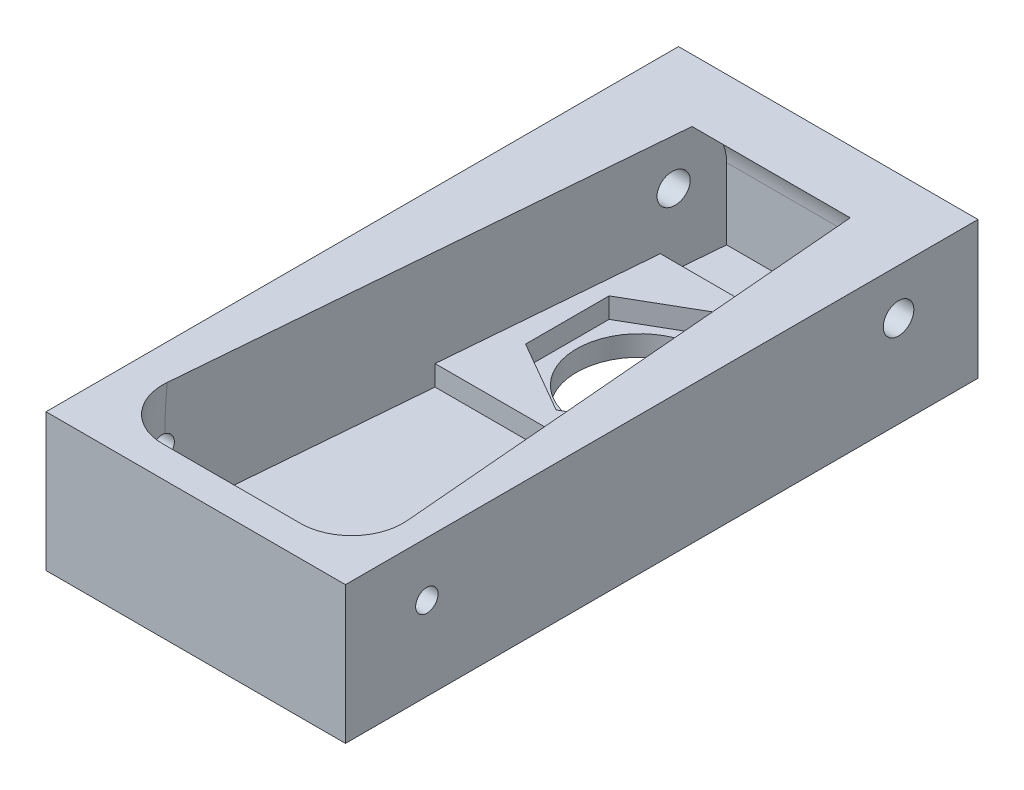
SolidWorks part; units mm, degrees
ref_plane "Front Plane" through (0, 0, 0) normal (0, 0, 1) x (1, 0, 0)
ref_plane "Top Plane" through (0, 0, 0) normal (0, 1, 0) x (1, 0, 0)
ref_plane "Right Plane" through (0, 0, 0) normal (1, 0, 0) x (0, 0, -1)
sketch "Sketch1" plane through (0, 0, 0) normal (0, 1, 0) x (1, 0, 0)
  line L0 (-15.3875, 18.6983) -> (-12.3875, 15.6983) construction
  line L1 (-12.3875, 15.6983) -> (12.0569, 15.6983) construction
  line L2 (-12.3875, 15.6983) -> (-12.3875, -40.3917) construction
  line L3 (-12.3875, -40.3917) -> (12.0569, -40.3917) construction
  line L4 (12.0569, 15.6983) -> (12.0569, -40.3917) construction
  line L5 (-15.3875, 18.6983) -> (14.0125, 18.6983)
  line L6 (-15.3875, 18.6983) -> (-15.3875, -43.3917)
  line L7 (-15.3875, -43.3917) -> (14.0125, -43.3917)
  line L8 (14.0125, 18.6983) -> (14.0125, -43.3917)
  line L9 (12.0569, -40.3917) -> (14.0125, -43.3917) construction
  line L10 (12.0569, 15.6983) -> (14.0125, 18.6983) construction
  line L11 (-12.3875, -40.3917) -> (-15.3875, -43.3917) construction
  line L12 (-12.3875, -40.3917) -> (-12.0875, -40.0917) construction
  line L13 (-12.0875, 15.3983) -> (11.7569, 15.3983) construction
  line L14 (-12.0875, 15.3983) -> (-12.0875, -40.0917) construction
  line L15 (-12.0875, -40.0917) -> (11.7569, -40.0917) construction
  line L16 (11.7569, 15.3983) -> (11.7569, -40.0917) construction
  line L17 (11.7569, -40.0917) -> (12.0569, -40.3917) construction
  line L18 (11.7569, 15.3983) -> (12.0569, 15.6983) construction
  line L19 (-12.3875, 15.6983) -> (-12.0875, 15.3983) construction
  line L20 (-7.6345, 15.6983) -> (-7.6345, 18.6983) construction
  line L21 (-12.3875, -10.0633) -> (-15.3875, -10.0633) construction
  line L22 (-7.6345, 15.6983) -> (-7.6345, 15.3983) construction
  line L23 (-12.3875, -10.0633) -> (-12.0875, -10.0633) construction
  line L24 (-15.3875, 18.6983) -> (14.0125, 18.6983) construction
  line L25 (14.0125, 18.6983) -> (14.0125, -43.3917) construction
  dimension "D1" = 3
  dimension "D2" = 0.3
extrude "Boss-Extrude1" add sketch "Sketch1" against normal blind 11.5
sketch "Sketch3" plane through (0, 0, 0) normal (1, 0, 0) x (0, 0, -1)
  line L3 (15.6983, -4.5) -> (15.6983, -55.7628)
  line L4 (15.6983, 0) -> (15.6983, -4.5) construction
  line L5 (15.6983, 0) -> (10.8983, 0) construction
  line L6 (15.6983, 0) -> (18.6983, 0) construction
  line L8 (-40.0905, 0) -> (-40.3917, 0)
  line L9 (12.5687, 0) -> (10.8983, 0)
  line L11 (10.8983, 0) -> (-40.0905, 0)
  arc A0 (-40.3917, 0) -> (15.6983, -55.7628) centre (10.8983, -4.5) ccw
  circle A1 centre (10.8983, -4.5) radius 1.5 construction
  circle A2 centre (10.8983, -4.5) radius 4.8 construction
  circle A3 centre (10.8983, -4.5) radius 4.5 construction
  circle A5 centre (10.8983, -4.5) radius 51.1871 construction
  arc A6 (15.6983, -4.5) -> (12.5687, 0) centre (10.8983, -4.5) ccw
  point P8 (0, 0)
  dimension "D1" = 3
  dimension "D2" = 3
  dimension "D3" = 0.3
  dimension "D4" = 3
  dimension "D5" = 0.3
extrude "Cut-Extrude2" cut sketch "Sketch3" against normal up to vertex (12.3875 mm away) and the other way up to vertex (12.0569 mm away) up to point (-12.3875, 0, -15.6983) other way up to point (12.0569, 0, -15.6983)
sketch "Sketch6" plane through (0, 0, 0) normal (0, 1, 0) x (1, 0, 0)
  line L0 (-12.3875, 15.6983) -> (-12.3875, -40.3917)
  line L1 (-12.3875, -40.3917) -> (-7.6653, 15.6983)
  line L3 (-7.6653, 15.6983) -> (-12.3875, 15.6983)
  line L4 (12.0569, 15.6983) -> (7.3347, 15.6983)
  line L5 (7.3347, 15.6983) -> (12.0569, -40.3917)
  line L6 (12.0569, -40.3917) -> (12.0569, 15.6983)
  dimension "D1" = 15
extrude "Boss-Extrude3" add sketch "Sketch6" against normal up to vertex (11.5 mm away) up to point (-12.3875, -11.5, -15.6983)
sketch "Sketch4" plane through (0, 0, 0) normal (1, 0, 0) x (0, 0, -1)
  circle A0 centre (10.8983, -4.5) radius 1.5
  circle A1 centre (10.8983, -4.5) radius 1.5 construction
  point P5 (8.8605, -5.2306)
extrude "Cut-Extrude3" cut sketch "Sketch4" against normal through all both and the other way through all
fillet "Fillet1" radius 5 2 edges at (-12.3875, -4.5, 40.5887) (12.0569, -4.5, 40.5887)
sketch "Sketch7" plane through (0, -11.5, 0) normal (0, -1, 0) x (-1, 0, 0)
  line L0 (0, 0) -> (0, 14.5109) construction
  line L1 (15.3875, 18.6983) -> (-14.0125, 18.6983)
  line L2 (15.3875, 18.6983) -> (15.3875, -43.3917)
  line L3 (15.3875, -43.3917) -> (-14.0125, -43.3917)
  line L4 (-14.0125, 18.6983) -> (-14.0125, -43.3917)
  line L8 (15.3875, 10.8983) -> (-14.0125, 10.8983) construction
  line L9 (-14.0125, 12.3983) -> (-14.0125, 9.3983) construction
  line L10 (15.3875, 7.8983) -> (-14.0125, 7.8983) construction
  circle A2 centre (0, -0.5017) radius 6.2
  point P8 (0, 0)
  dimension "D1" = 12.4
  dimension "D2" = 3
  dimension "D3" = 19.2
extrude "Boss-Extrude4" add sketch "Sketch7" along normal blind 2
sketch "Sketch8" plane through (0, -11.5, 0) normal (0, 1, 0) x (1, 0, 0)
  line L1 (-9.8878, -10.7) -> (9.5572, -10.7)
  line L4 (-11.9032, -34.6392) -> (-7.6653, 15.6983) construction
  line L6 (7.3347, 15.6983) -> (11.5726, -34.6392) construction
  line L11 (9.5572, -10.7) -> (7.9145, 9.6967)
  line L12 (7.1, -4.6008) -> (7.1, 3.5975)
  line L13 (7.1, 3.5975) -> (0, 7.6967)
  line L14 (0, 7.6967) -> (-7.1, 3.5975)
  line L15 (-7.1, 3.5975) -> (-7.1, -4.6008)
  line L16 (-7.1, -4.6008) -> (0, -8.7)
  line L17 (0, -8.7) -> (7.1, -4.6008)
  line L18 (7.9145, 9.6967) -> (-8.2451, 9.6967)
  line L19 (-8.2451, 9.6967) -> (-9.8878, -10.7)
  circle A0 centre (0, -0.5017) radius 7.1 construction
  dimension "D1" = 14.2
  dimension "D2" = 2
  dimension "D3" = 2
extrude "Boss-Extrude5" add sketch "Sketch8" along normal blind 2
sketch "Sketch9" plane through (-15.3875, 0, 0) normal (-1, 0, 0) x (0, 0, 1)
  line L0 (-10.8983, -4.5) -> (35.4034, -5.3238) construction
  line L2 (35.2331, -8.5516) -> (-10.8983, -4.5) construction
  circle A0 centre (35.4034, -5.3238) radius 1.1
  arc A1 (34.0036, -5.2989) -> (36.8032, -5.3487) centre (35.4034, -5.3238) cw construction
  arc A2 (34.0036, -5.2989) -> (33.8385, -8.4291) centre (-10.8983, -4.5) cw construction
  arc A3 (36.8032, -5.3487) -> (36.6278, -8.6741) centre (-10.8983, -4.5) cw construction
  arc A4 (36.6278, -8.6741) -> (33.8385, -8.4291) centre (35.2331, -8.5516) cw construction
  point P2 (0, 0)
  point P3 (35.2255, -8.6686)
  dimension "D1" = 2.2
  dimension "D3" = 4
  dimension "D2" = 0.3
extrude "Cut-Extrude4" cut sketch "Sketch9" against normal through all
